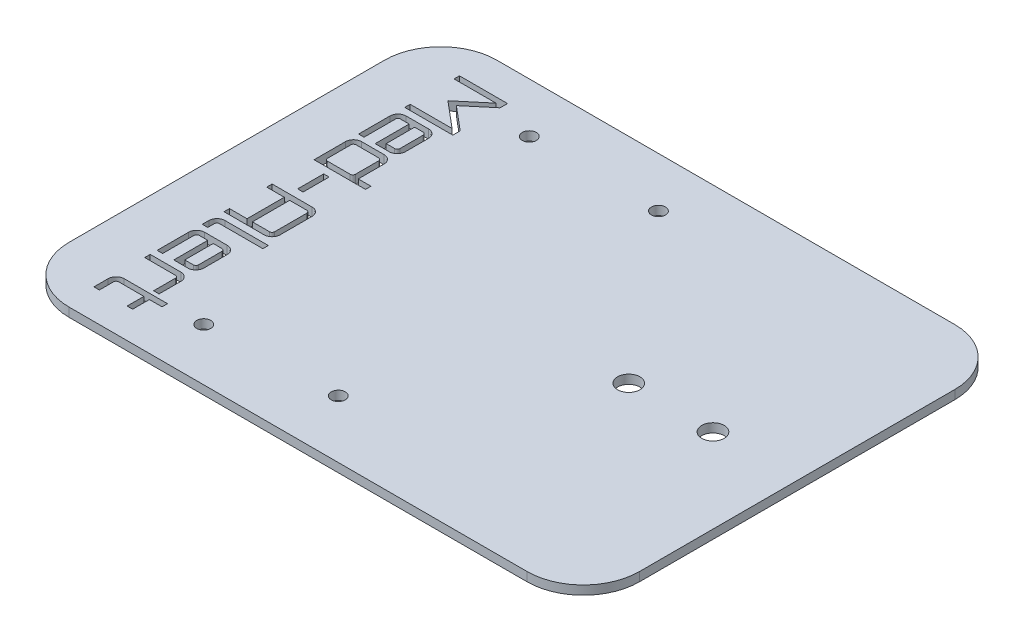
SolidWorks part; units mm, degrees
ref_plane "Front Plane" through (0, 0, 0) normal (0, 0, 1) x (1, 0, 0)
ref_plane "Top Plane" through (0, 0, 0) normal (0, 1, 0) x (1, 0, 0)
ref_plane "Right Plane" through (0, 0, 0) normal (1, 0, 0) x (0, 0, -1)
sketch "Sketch1" plane through (0, 0, 0) normal (0, 1, 0) x (1, 0, 0)
  line L1 (50.8, -38.1) -> (-50.8, -38.1)
  line L2 (50.8, -38.1) -> (50.8, 38.1)
  line L3 (50.8, 38.1) -> (-50.8, 38.1)
  line L4 (-50.8, -38.1) -> (-50.8, 38.1)
  line L5 (50.8, -38.1) -> (-50.8, 38.1) construction
  line L6 (50.8, 38.1) -> (-50.8, -38.1) construction
  point P0 (0, 0)
  dimension "D1" = 101.6
  dimension "D2" = 76.2
extrude "Boss-Extrude1" add sketch "Sketch1" along normal blind 1.5875
sketch "Sketch2" plane through (0, 1.5875, 0) normal (0, 1, 0) x (1, 0, 0)
  line L0 (-14.025, 0) -> (14.025, 0) construction
  line L1 (50.8, -38.1) -> (50.8, 38.1) construction
  circle A0 centre (35.8, 0) radius 2
  circle A1 centre (20.8, 0) radius 2
  dimension "D1" = 4
  dimension "D2" = 4
  dimension "D3" = 15
  dimension "D4" = 15
extrude "Cut-Extrude1" cut sketch "Sketch2" against normal through all
fillet "Fillet1" radius 10 4 edges at (-50.8, 0.7937, -38.1) (-50.8, 0.7937, 38.1) (50.8, 0.7937, 38.1) (50.8, 0.7937, -38.1)
sketch "Sketch4" plane through (0, 1.5875, 0) normal (0, 1, 0) x (1, 0, 0)
  circle A0 centre (-3.1344, 29.2185) radius 1.25
  circle A1 centre (-3.1344, -27.8181) radius 1.25
  circle A2 centre (-26.1344, 29.2185) radius 1.25
  circle A3 centre (-26.1344, -28.7815) radius 1.25
  dimension "D1" = 2.5
  dimension "D2" = 2.5
  dimension "D3" = 2.5
  dimension "D4" = 2.5
  dimension "D5" = 23
  dimension "D6" = 23
  dimension "D7" = 58
extrude "Cut-Extrude2" cut sketch "Sketch4" against normal through all
sketch "Sketch5" plane through (0, 1.5875, 0) normal (0, 1, 0) x (1, 0, 0)
  line L1 (-41.7142, 38.1) -> (-41.7142, -38.1) construction
  line L2 (40.8, 38.1) -> (-40.8, 38.1) construction
  line L3 (-40.8, -38.1) -> (40.8, -38.1) construction
  text T0 "Med-Alert" font "Orbitron" height in points 24
extrude "Cut-Extrude3" cut sketch "Sketch5" against normal blind 1.5875
